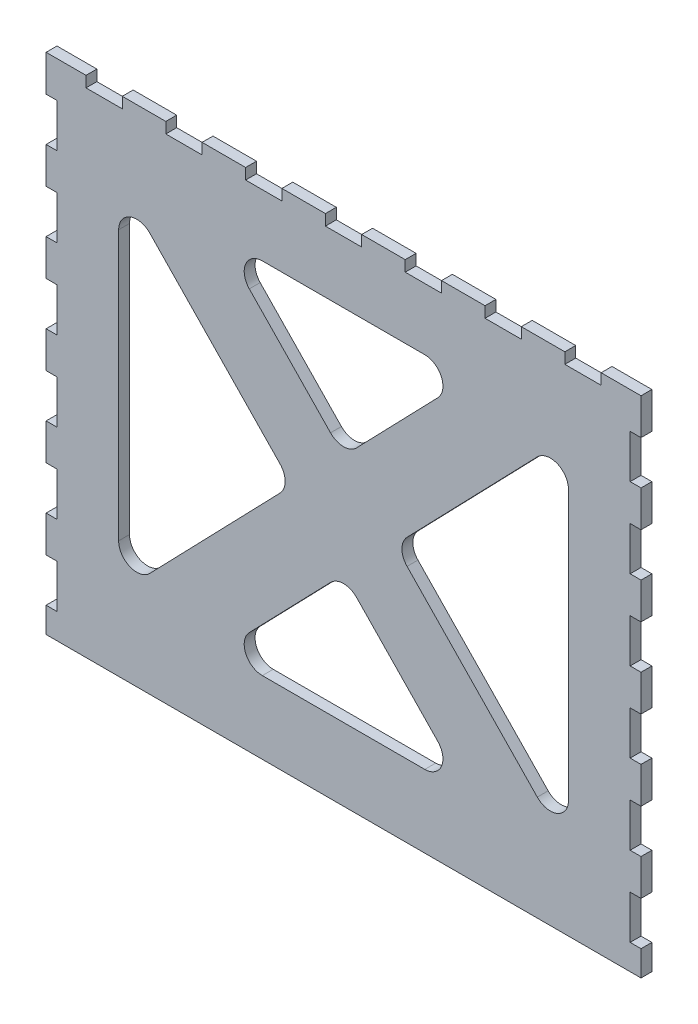
SolidWorks part; units mm, degrees
material "birch 3mm plywood"
ref_plane "Front Plane" through (0, 0, 0) normal (0, 0, 1) x (1, 0, 0)
ref_plane "Top Plane" through (0, 0, 0) normal (0, 1, 0) x (1, 0, 0)
ref_plane "Right Plane" through (0, 0, 0) normal (1, 0, 0) x (0, 0, -1)
sketch "Sketch1" plane through (0, 0, 152) normal (0, 0, 1) x (1, 0, 0)
  line L1 (-82, 69.5) -> (82, 69.5)
  line L2 (-82, 69.5) -> (-82, -69.5)
  line L3 (-82, -69.5) -> (82, -69.5)
  line L4 (82, 69.5) -> (82, -69.5)
  line L6 (-62, -37.1347) -> (-62, 37.1347)
  line L7 (-53.4053, 40.61) -> (-17.504, 3.4753)
  line L12 (75, -62.5) -> (-75, -62.5) construction
  line L13 (75, 62.5) -> (75, -62.5) construction
  line L14 (-75, -62.5) -> (-75, 62.5) construction
  line L15 (-75, 62.5) -> (75, 62.5) construction
  line L18 (22.3929, 49.5) -> (-22.3929, 49.5)
  line L19 (-17.504, -3.4753) -> (-53.4053, -40.61)
  line L20 (-25.9877, 41.0247) -> (-3.5947, 17.8624)
  line L21 (3.5947, 17.8624) -> (25.9877, 41.0247)
  line L23 (53.4053, 40.61) -> (17.504, 3.4753)
  line L24 (62, -37.1347) -> (62, 37.1347)
  line L25 (17.504, -3.4753) -> (53.4053, -40.61)
  line L26 (-75, 0) -> (75, 0) construction
  line L27 (-25.9877, -41.0247) -> (-3.5947, -17.8624)
  line L28 (22.3929, -49.5) -> (-22.3929, -49.5)
  line L29 (3.5947, -17.8624) -> (25.9877, -41.0247)
  line L30 (0, 14.1442) -> (0, -14.1442) construction
  line L31 (-14.1442, 0) -> (14.1442, 0) construction
  line L32 (0, 14.1442) -> (0, -14.1442) construction
  arc A0 (-53.4053, -40.61) -> (-62, -37.1347) centre (-57, -37.1347) cw
  arc A1 (-17.504, -3.4753) -> (-17.504, 3.4753) centre (-21.0988, 0) ccw
  arc A2 (-53.4053, 40.61) -> (-62, 37.1347) centre (-57, 37.1347) ccw
  arc A3 (25.9877, -41.0247) -> (22.3929, -49.5) centre (22.3929, -44.5) cw
  arc A4 (-25.9877, -41.0247) -> (-22.3929, -49.5) centre (-22.3929, -44.5) ccw
  arc A5 (-3.5947, -17.8624) -> (3.5947, -17.8624) centre (0, -21.3377) cw
  arc A6 (17.504, 3.4753) -> (17.504, -3.4753) centre (21.0988, 0) ccw
  arc A7 (53.4053, -40.61) -> (62, -37.1347) centre (57, -37.1347) ccw
  arc A8 (62, 37.1347) -> (53.4053, 40.61) centre (57, 37.1347) ccw
  arc A9 (-25.9877, 41.0247) -> (-22.3929, 49.5) centre (-22.3929, 44.5) cw
  arc A10 (25.9877, 41.0247) -> (22.3929, 49.5) centre (22.3929, 44.5) ccw
  arc A11 (3.5947, 17.8624) -> (-3.5947, 17.8624) centre (0, 21.3377) cw
  point P14 (0, 0)
  point P15 (0, 0)
  point P32 (-62, 49.5)
  point P35 (34.1815, -49.5)
  point P38 (-34.1815, -49.5)
  point P51 (-34.1815, 49.5)
  point P54 (34.1815, 49.5)
  dimension "D9" = 5
  dimension "D10" = 5
  dimension "D2" = 20
  dimension "D3" = 7
  dimension "D4" = 7
  dimension "D5" = 20
  dimension "D6" = 20
  dimension "D7" = 20
  dimension "D8" = 20
  dimension "D11" = 150
  dimension "D12" = 125
  dimension "D13" = 7
extrude "Boss-Extrude1" add sketch "Sketch1" along normal blind 3
sketch "Sketch2" plane through (0, 0, 155) normal (0, 0, 1) x (1, 0, 0)
  line L0 (0, 69.5) -> (0, -69.5) construction
  line L1 (17, 69.5) -> (17, 66.5)
  line L2 (-5, 69.5) -> (5, 69.5)
  line L3 (-5, 69.5) -> (-5, 66.5)
  line L4 (-82, 69.5) -> (-82, -69.5)
  line L5 (-82, -69.5) -> (82, -69.5)
  line L6 (82, -69.5) -> (82, 69.5)
  line L7 (82, 69.5) -> (-82, 69.5)
  line L8 (-82, 69.5) -> (-82, -69.5)
  line L9 (-82, -69.5) -> (82, -69.5)
  line L10 (82, -69.5) -> (82, 69.5)
  line L11 (82, 69.5) -> (-82, 69.5)
  line L12 (-5, 66.5) -> (5, 66.5)
  line L13 (5, 69.5) -> (5, 66.5)
  line L14 (17, 69.5) -> (27, 69.5)
  line L15 (27, 69.5) -> (27, 66.5)
  line L16 (17, 66.5) -> (27, 66.5)
  line L17 (39, 69.5) -> (39, 66.5)
  line L18 (39, 69.5) -> (49, 69.5)
  line L19 (49, 69.5) -> (49, 66.5)
  line L20 (39, 66.5) -> (49, 66.5)
  line L21 (61, 69.5) -> (61, 66.5)
  line L22 (61, 69.5) -> (71, 69.5)
  line L23 (71, 69.5) -> (71, 66.5)
  line L24 (61, 66.5) -> (71, 66.5)
  line L25 (-27, 69.5) -> (-27, 66.5)
  line L26 (-27, 69.5) -> (-17, 69.5)
  line L27 (-17, 69.5) -> (-17, 66.5)
  line L28 (-27, 66.5) -> (-17, 66.5)
  line L29 (-49, 69.5) -> (-49, 66.5)
  line L30 (-49, 69.5) -> (-39, 69.5)
  line L31 (-39, 69.5) -> (-39, 66.5)
  line L32 (-49, 66.5) -> (-39, 66.5)
  line L33 (-71, 69.5) -> (-71, 66.5)
  line L34 (-71, 69.5) -> (-61, 69.5)
  line L35 (-61, 69.5) -> (-61, 66.5)
  line L36 (-71, 66.5) -> (-61, 66.5)
  line L37 (-82, 37.5) -> (-82, 25.5)
  line L38 (-82, 59.5) -> (-79, 59.5)
  line L39 (-82, 59.5) -> (-82, 47.5)
  line L40 (-82, 47.5) -> (-79, 47.5)
  line L41 (-79, 59.5) -> (-79, 47.5)
  line L42 (-82, 37.5) -> (-79, 37.5)
  line L43 (-79, 37.5) -> (-79, 25.5)
  line L44 (-82, 25.5) -> (-79, 25.5)
  line L45 (-82, 15.5) -> (-82, 3.5)
  line L46 (-82, 15.5) -> (-79, 15.5)
  line L47 (-79, 15.5) -> (-79, 3.5)
  line L48 (-82, 3.5) -> (-79, 3.5)
  line L49 (-82, -6.5) -> (-82, -18.5)
  line L50 (-82, -6.5) -> (-79, -6.5)
  line L51 (-79, -6.5) -> (-79, -18.5)
  line L52 (-82, -18.5) -> (-79, -18.5)
  line L53 (-82, -28.5) -> (-82, -40.5)
  line L54 (-82, -28.5) -> (-79, -28.5)
  line L55 (-79, -28.5) -> (-79, -40.5)
  line L56 (-82, -40.5) -> (-79, -40.5)
  line L57 (-82, -50.5) -> (-82, -62.5)
  line L58 (-82, -50.5) -> (-79, -50.5)
  line L59 (-79, -50.5) -> (-79, -62.5)
  line L60 (-82, -62.5) -> (-79, -62.5)
  line L65 (82, -50.5) -> (79, -50.5)
  line L66 (79, -50.5) -> (79, -62.5)
  line L67 (82, -62.5) -> (79, -62.5)
  line L68 (82, -50.5) -> (82, -62.5)
  line L69 (82, -28.5) -> (79, -28.5)
  line L70 (79, -28.5) -> (79, -40.5)
  line L71 (82, -40.5) -> (79, -40.5)
  line L72 (82, -28.5) -> (82, -40.5)
  line L73 (82, -6.5) -> (79, -6.5)
  line L74 (79, -6.5) -> (79, -18.5)
  line L75 (82, -18.5) -> (79, -18.5)
  line L76 (82, -6.5) -> (82, -18.5)
  line L77 (82, 15.5) -> (79, 15.5)
  line L78 (79, 15.5) -> (79, 3.5)
  line L79 (82, 3.5) -> (79, 3.5)
  line L80 (82, 15.5) -> (82, 3.5)
  line L81 (82, 37.5) -> (79, 37.5)
  line L82 (79, 37.5) -> (79, 25.5)
  line L83 (82, 25.5) -> (79, 25.5)
  line L84 (82, 37.5) -> (82, 25.5)
  line L85 (82, 47.5) -> (79, 47.5)
  line L86 (79, 59.5) -> (79, 47.5)
  line L87 (82, 59.5) -> (79, 59.5)
  line L88 (82, 59.5) -> (82, 47.5)
  point P10 (0, 66.5)
  line M64 (82, -69.5) -> (82, 69.5)
  line M65 (82, 69.5) -> (-82, 69.5)
  dimension "D2" = 10
  dimension "D3" = 3
  dimension "D6" = 12
  dimension "D7" = 12
  dimension "D8" = 3
  dimension "D9" = 12
  dimension "D10" = 10
  dimension "D12" = 10
  dimension "D1" = 0
  dimension "D4" = 4
  dimension "D5" = 4
  dimension "D11" = 6
extrude "Cut-Extrude1" cut sketch "Sketch2" against normal blind 10 contours L8 L44 L43 L42 | L33 L36 L35 L11 | L29 L32 L31 M65 | L25 L28 L27 L11 | L0 L12 L13 M65 | L0 L11 L3 L12 | L1 L16 L15 L11 | L17 L20 L19 L11 | L21 L24 L23 L11 | L87 L86 L85 M64 | L79 L77 L78 M64 | L75 L10 L73 L74 | L71 L69 L70 M64 | L67 L10 L65 L66 | L41 L40 L39 L38 | L47 L48 L45 L46 | L51 L52 L49 L50 | L55 L56 L53 L54 | L59 L60 L57 L58 | L82 L83 L84 L81 region at (2.5, 68, 155) region at (-2.5, 68, 155) region at (-22, 68, 155) region at (22, 68, 155) region at (80.5, -56.5, 155) region at (-44, 68, 155) region at (44, 68, 155) region at (80.5, -34.5, 155) region at (-66, 68, 155) region at (66, 68, 155) region at (80.5, -12.5, 155) region at (80.5, 53.5, 155) region at (80.5, 9.5, 155) region at (-80.5, 31.5, 155)
